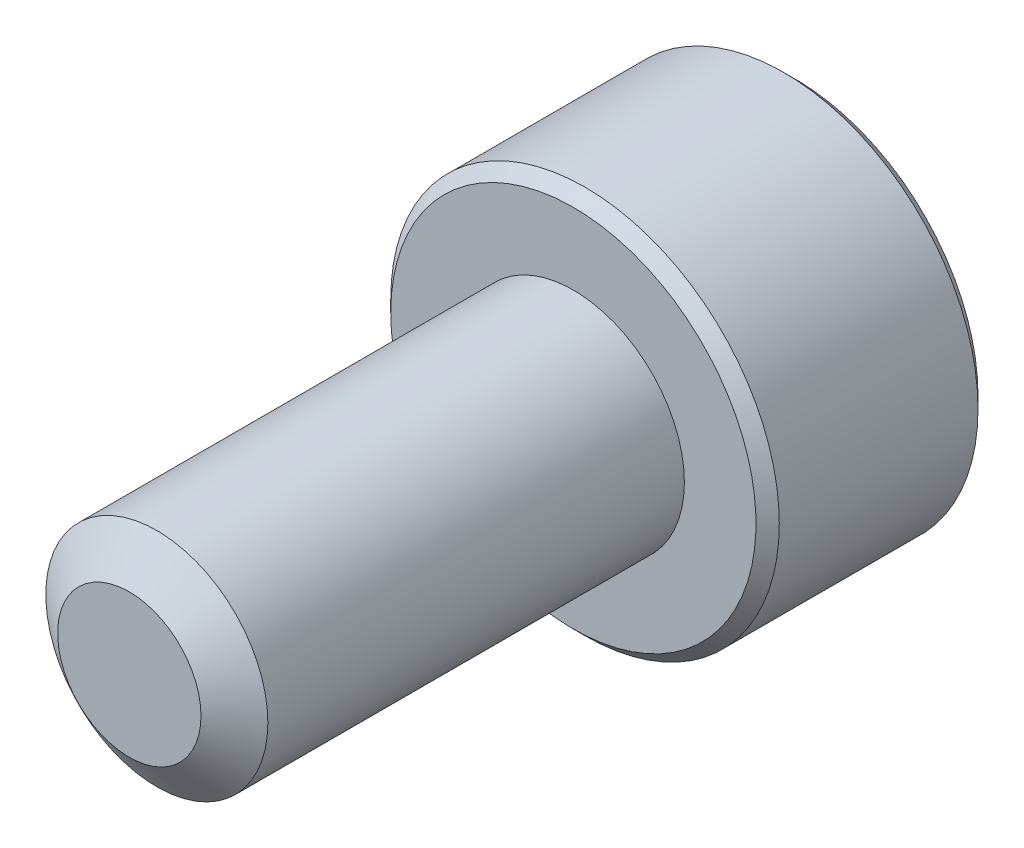
SolidWorks part; units mm, degrees
material "Alloy Steel"
ref_plane "Front Plane" through (0, 0, 0) normal (0, 0, 1) x (1, 0, 0)
ref_plane "Top Plane" through (0, 0, 0) normal (0, 1, 0) x (1, 0, 0)
ref_plane "Right Plane" through (0, 0, 0) normal (1, 0, 0) x (0, 0, -1)
sketch "Sketch1" plane through (0, 0, 0) normal (0, 0, 1) x (1, 0, 0)
  circle A0 centre (0, 0) radius 2
  dimension "OD" = 4
extrude "Extrude1" add sketch "Sketch1" against normal blind 8
sketch "Sketch2" plane through (0, 0, 0) normal (0, 0, 1) x (1, 0, 0)
  circle A0 centre (0, 0) radius 2 construction
  circle A1 centre (0, 0) radius 2
curve "Helix/Spiral1" [suppressed] pitch 0.7 height 8.7 turns 12.4286 parameters "pitch"=0.7
sketch "Sketch3" plane through (0, 0, 0) normal (1, 0, 0) x (0, 0, -1)
  line L0 (-0.6125, 2) -> (-0.35, 1.5453)
  line L1 (-0.35, 1.5453) -> (-0.2625, 1.5453)
  line L2 (-0.2625, 1.5453) -> (0, 2)
  line L3 (-0.6125, 2) -> (0, 2)
  line L4 (-0.3063, 2) -> (-0.3063, 1.5453) construction
  line L5 (-0.4813, 1.7727) -> (-0.1313, 1.7727) construction
  line L6 (0, 2) -> (0, -2) construction
  line L7 (0, -2) -> (8, -2) construction
  point P11 (3.15, -2)
  dimension "D1" = 0.0875
  dimension "D2" = 0.35
  dimension "D3" = 60
  dimension "D4" = 3.15
sweep "Cut-Sweep1" [suppressed] cut profiles "Sketch3" path "Helix/Spiral1"
sketch "Sketch4" plane through (0, 0, 0) normal (1, 0, 0) x (0, 0, -1)
  line L0 (0.4962, 2) -> (0, 1.2913)
  line L1 (0, 1.2913) -> (0, 2)
  line L2 (0.4962, 2) -> (0, 2)
  line L3 (-0.6125, 2) -> (0, 2) construction
  line L4 (0, 0) -> (7.0209, 0) construction
  dimension "D1" = 55
  dimension "D2" = 0.254
revolve "Cut-Revolve1" cut sketch "Sketch4" angle 360 about L4
sketch "Sketch5" [suppressed] plane through (0, 0, 0) normal (1, 0, 0) x (0, 0, -1)
  line L0 (8, -0.6429) -> (8, 1.6418) construction
  line L1 (8, 2) -> (0.1203, 2)
  line L2 (8, 2) -> (8, 0)
  line L3 (8, 0) -> (0.0001, 0)
  line L4 (0.0001, 1.6698) -> (0.0001, 0)
  line L5 (0.1203, 2) -> (0.0001, 1.6698)
  line L6 (0, 0) -> (9.9695, 0) construction
  point P3 (0.0001, 2)
  point P10 (0.0001, 2)
  dimension "D1" = 0.3302
  dimension "Thread min" = 0.0001
  dimension "D3" = 20
revolve "partially thread" [suppressed] add sketch "Sketch5" angle 360 about L6
sketch "Sketch6" plane through (0, 0, -8) normal (0, 0, -1) x (-1, 0, 0)
  circle A0 centre (0, 0) radius 3.5
  dimension "head dia" = 7
extrude "Extrude2" add sketch "Sketch6" along normal blind 4
sketch "Sketch7" plane through (0, 0, -12) normal (0, 0, -1) x (-1, 0, 0)
  line L1 (0, 1.7321) -> (-1.5, 0.866)
  line L2 (-1.5, 0.866) -> (-1.5, -0.866)
  line L3 (-1.5, -0.866) -> (0, -1.7321)
  line L4 (0, -1.7321) -> (1.5, -0.866)
  line L5 (1.5, -0.866) -> (1.5, 0.866)
  line L6 (1.5, 0.866) -> (0, 1.7321)
  circle A0 centre (0, 0) radius 1.5 construction
  dimension "hex dia" = 3
extrude "Cut-Extrude1" cut sketch "Sketch7" against normal blind 2.25
sketch "Sketch8" plane through (0, 0, -12) normal (0, 0, -1) x (-1, 0, 0)
  circle A0 centre (0, 0) radius 1.7321
extrude "Cut-Extrude2" cut sketch "Sketch8" against normal through all draft 45
chamfer "Chamfer1" distance 0.21 angle 45 2 edges at (-3.5, 0, -12) (-3.5, 0, -8)
sketch "Sketch9" plane through (0, 0, 0) normal (1, 0, 0) x (0, 0, -1)
  line L0 (0, 2) -> (0, -2) construction
  line L1 (3.85, 2) -> (3.85, -2) construction
  dimension "D1" = 3.85
sketch "Sketch10" plane through (0, 0, 0) normal (1, 0, 0) x (0, 0, -1)
  line L0 (8, 2) -> (8, 0)
  line L1 (8, 2) -> (7.825, 2)
  line L2 (7.825, 2) -> (6.9966, 0)
  line L3 (8, 0) -> (6.9966, 0)
  line L4 (8, 3.29) -> (8, -3.29) construction
  dimension "D1" = 22.5
  dimension "D2" = 0.175
revolve "Revolve1" add sketch "Sketch10" angle 360 about L3
equation "\"D3@Helix/Spiral1\" = \"screw length@Extrude1\"+\"pitch@Helix/Spiral1\""
equation "\"D1@Sketch3\" = \"pitch@Helix/Spiral1\"*.125"
equation "\"D2@Sketch3\" = \"pitch@Helix/Spiral1\"*.5"
equation "\"D1@Cut-Extrude1\" = \"hex dia@Sketch7\"*.75"
equation "\"D1@Chamfer1\" = \"head dia@Sketch6\"*.03"
equation "\"D1@Sketch9\" = \"pitch@Helix/Spiral1\"*5.5"
equation "\"D2@Sketch10\" = \"pitch@Helix/Spiral1\"*.25"
equation "\"D4@Sketch3\" = \"pitch@Helix/Spiral1\"*4.50"
